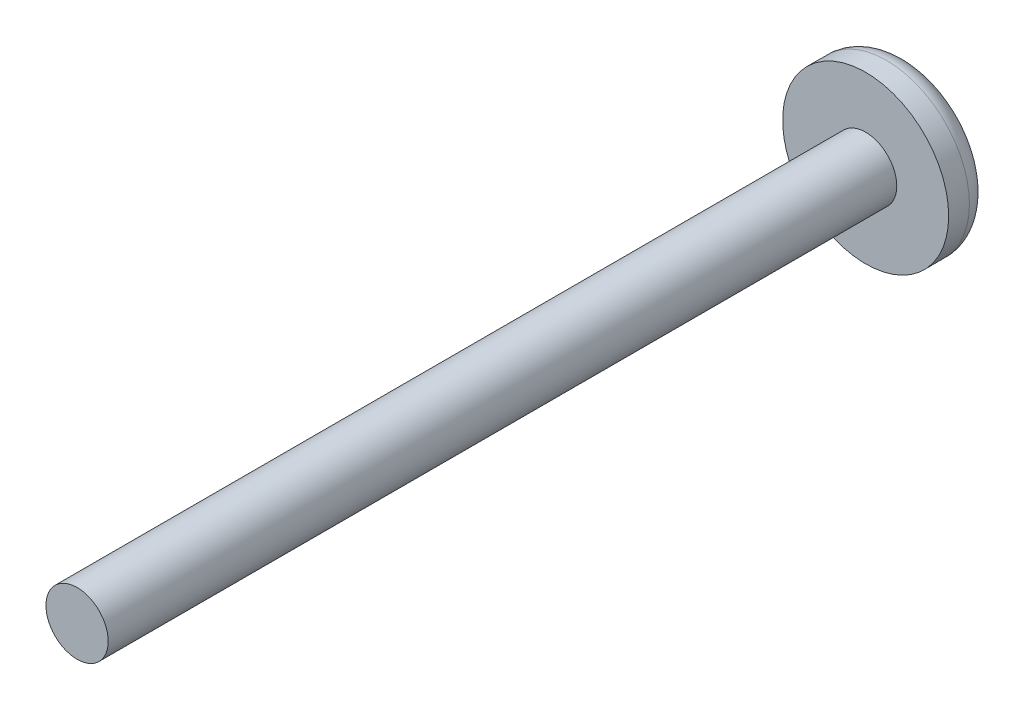
SolidWorks part; units mm, degrees
ref_plane "Front Plane" through (0, 0, 0) normal (0, 0, 1) x (1, 0, 0)
ref_plane "Top Plane" through (0, 0, 0) normal (0, 1, 0) x (1, 0, 0)
ref_plane "Right Plane" through (0, 0, 0) normal (1, 0, 0) x (0, 0, -1)
sketch "Sketch1" plane through (0, 0, 0) normal (0, 1, 0) x (1, 0, 0)
  line L0 (0, 0) -> (0, 40)
  line L1 (0, 0) -> (1.5, 0)
  line L4 (1.5, 0) -> (1.5, 38)
  line L5 (0, 40) -> (4, 40)
  line L7 (1.5, 38) -> (4, 38)
  line L8 (4, 40) -> (4, 38)
  point P2 (0, 0)
  dimension "D1" = 4
  dimension "D2" = 40
  dimension "D3" = 2
  dimension "D4" = 1.5
revolve "Revolve1" add sketch "Sketch1" angle 360 about L0
fillet "Fillet1" radius 1 1 edges at (4, 0, -40) type face fillet first side face at (4, 0, -40) second side face at (4, 0, -40)
